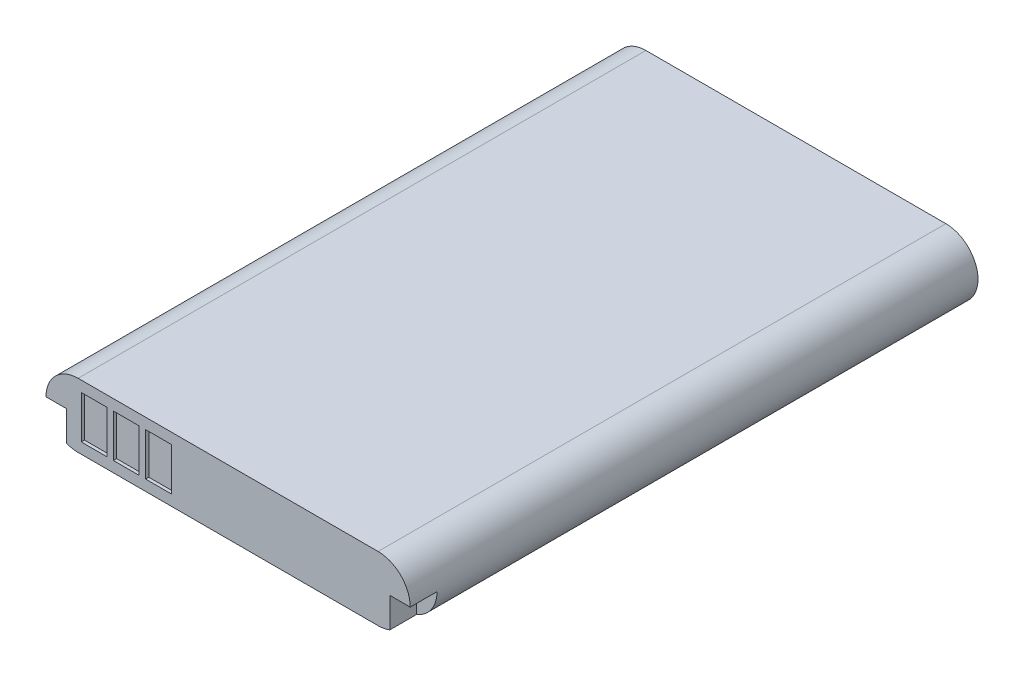
SolidWorks part; units mm, degrees
ref_plane "Front Plane" through (0, 0, 0) normal (0, 0, 1) x (1, 0, 0)
ref_plane "Top Plane" through (0, 0, 0) normal (0, 1, 0) x (1, 0, 0)
ref_plane "Right Plane" through (0, 0, 0) normal (1, 0, 0) x (0, 0, -1)
sketch "Sketch1" plane through (0, 0, 0) normal (0, 0, 1) x (1, 0, 0)
  line L0 (-14, 0) -> (14, 0) construction
  line L1 (-14, 3) -> (14, 3)
  line L2 (-14, -3) -> (14, -3)
  arc A0 (-14, 3) -> (-14, -3) centre (-14, 0) ccw
  arc A1 (14, -3) -> (14, 3) centre (14, 0) ccw
  point P3 (0, 0)
  point P8 (-17, 0)
  point P9 (17, 0)
  dimension "D1" = 6
  dimension "D2" = 34
extrude "Boss-Extrude1" add sketch "Sketch1" along normal blind 53
sketch "Sketch2" plane through (0, 0, 53) normal (0, 0, 1) x (1, 0, 0)
  line L0 (-11.3, 0) -> (0, 0) construction
  line L1 (-13.7, 2) -> (-11.3, 2)
  line L2 (-13.7, 2) -> (-13.7, -2)
  line L3 (-13.7, -2) -> (-11.3, -2)
  line L4 (-11.3, 2) -> (-11.3, -2)
  line L5 (-8.3, 2) -> (-8.3, -2)
  line L6 (-10.7, -2) -> (-8.3, -2)
  line L7 (-10.7, 2) -> (-10.7, -2)
  line L8 (-10.7, 2) -> (-8.3, 2)
  line L9 (-5.3, 2) -> (-5.3, -2)
  line L10 (-7.7, -2) -> (-5.3, -2)
  line L11 (-7.7, 2) -> (-7.7, -2)
  line L12 (-7.7, 2) -> (-5.3, 2)
  arc A0 (-14, 3) -> (-14, -3) centre (-14, 0) ccw construction
  point P4 (0, 0)
  point P5 (-12.5, -2)
  point P18 (-17, 0)
  point P19 (-12.5, 2)
  point P22 (-9.5, -2)
  dimension "D1" = 4
  dimension "D2" = 4.5
  dimension "D3" = 2.4
  dimension "D5" = 3
  dimension "D4" = 3
extrude "Cut-Extrude1" cut sketch "Sketch2" against normal blind 0.3
sketch "Sketch3" plane through (0, 0, 53) normal (0, 0, 1) x (1, 0, 0)
  line L0 (0, 0) -> (0, -3) construction
  line L1 (-19.1, 0) -> (-15.1, 0)
  line L2 (-19.1, 0) -> (-19.1, -4)
  line L3 (-19.1, -4) -> (-15.1, -4)
  line L4 (-15.1, 0) -> (-15.1, -4)
  line L5 (-14, -3) -> (14, -3) construction
  line L6 (19.1, 0) -> (15.1, 0)
  line L7 (19.1, 0) -> (19.1, -4)
  line L8 (19.1, -4) -> (15.1, -4)
  line L9 (15.1, 0) -> (15.1, -4)
  arc A0 (-14, 3) -> (-14, -3) centre (-14, 0) ccw construction
  point P7 (-17, 0)
  dimension "D1" = 30.2
  dimension "D2" = 4
extrude "Cut-Extrude2" cut sketch "Sketch3" against normal blind 2.5
